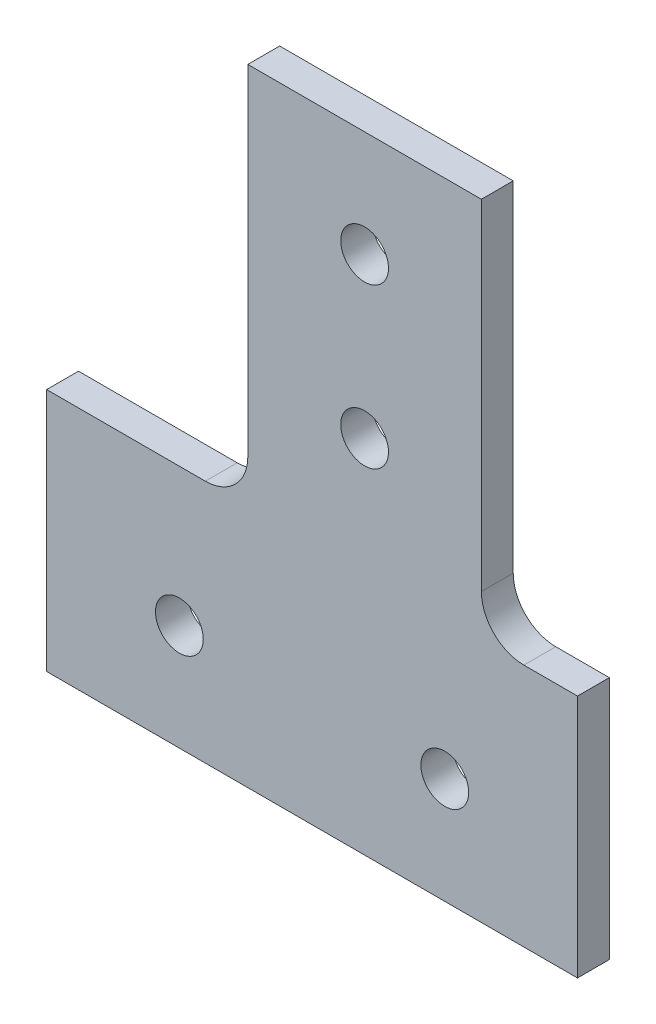
SolidWorks part; units mm, degrees
ref_plane "Ebene vorne" through (0, 0, 0) normal (0, 0, 1) x (1, 0, 0)
ref_plane "Ebene oben" through (0, 0, 0) normal (0, 1, 0) x (1, 0, 0)
ref_plane "Ebene rechts" through (0, 0, 0) normal (1, 0, 0) x (0, 0, -1)
sketch "Skizze1" plane through (0, 0, 0) normal (0, 0, 1) x (1, 0, 0)
  line L0 (-10.0526, 11.5) -> (-25, 11.5)
  line L1 (25, -11.5) -> (-25, -11.5)
  line L2 (25, -11.5) -> (25, 11.5)
  line L3 (25, 11.5) -> (19.9474, 11.5)
  line L4 (-25, -11.5) -> (-25, 11.5)
  line L5 (25, -11.5) -> (-25, 11.5) construction
  line L6 (25, 11.5) -> (-25, -11.5) construction
  line L8 (15.9474, 15.5) -> (15.9474, 71.5)
  line L9 (15.9474, 71.5) -> (-6.0526, 71.5)
  line L10 (-6.0526, 15.5) -> (-6.0526, 71.5)
  arc A0 (19.9474, 11.5) -> (15.9474, 15.5) centre (19.9474, 15.5) cw
  arc A1 (-10.0526, 11.5) -> (-6.0526, 15.5) centre (-10.0526, 15.5) ccw
  point P0 (0, 0)
  point P12 (15.9474, 11.5)
  point P15 (-6.0526, 11.5)
  dimension "D5" = 4
  dimension "D1" = 23
  dimension "D2" = 50
  dimension "D3" = 60
  dimension "D4" = 22
  dimension "D6" = 9.0526
extrude "Aufsatz-Linear austragen1" add sketch "Skizze1" along normal blind 3
hole_wizard "Durchgangsloch für M41" positions "Skizze2" profile "Skizze3" hole size "M4" standard "ANSI Metric" end condition through all
sketch "Skizze2" plane through (0, 0, 3) normal (0, 0, 1) x (1, 0, 0)
  line L1 (4.9474, 53.4879) -> (4.9474, -32.4603) construction
  line L4 (15.9474, 71.5) -> (-6.0526, 71.5) construction
  point P11 (4.9474, 37.5)
  point P13 (4.9474, 22.5)
  dimension "D1" = 15
  dimension "D2" = 34
sketch "Skizze3" plane through (4.9474, 22.5, 3) normal (1, 0, 0) x (0, -1, 0)
  line L0 (0, 0) -> (0, 3)
  line L1 (0, 3) -> (2.25, 3)
  line L2 (2.25, 3) -> (2.25, 0)
  line L5 (2.25, 0) -> (0, 0)
  line L11 (0, -6.35) -> (0, 107.95) construction
  dimension "Bohrerdurchmesser" = 4.5
  dimension "Bohrungstiefe" = 3
hole_wizard "Durchgangsloch für M42" positions "Skizze4" profile "Skizze5" hole size "M4" standard "ANSI Metric" end condition through all
sketch "Skizze4" plane through (0, 0, 3) normal (0, 0, 1) x (1, 0, 0)
  line L3 (0, -11.5) -> (0, -14.3794) construction
  line L7 (-12.5, -1.5) -> (49987.5, -1.5) construction
  line L8 (-25, -11.5) -> (25, -11.5) construction
  point P10 (-12.5, -1.5)
  point P12 (12.5, -1.5)
  dimension "D1" = 25
  dimension "D2" = 12.5
  dimension "D3" = 10
sketch "Skizze5" plane through (-12.5, -1.5, 3) normal (1, 0, 0) x (0, -1, 0)
  line L0 (0, 0) -> (0, 3)
  line L1 (0, 3) -> (2.25, 3)
  line L2 (2.25, 3) -> (2.25, 0)
  line L5 (2.25, 0) -> (0, 0)
  line L11 (0, -6.35) -> (0, 107.95) construction
  dimension "Bohrerdurchmesser" = 4.5
  dimension "Bohrungstiefe" = 3
sketch "Skizze6" plane through (0, 0, 3) normal (0, 0, 1) x (1, 0, 0)
  line L0 (-6.0526, 71.5) -> (15.9474, 71.5)
  line L1 (15.9474, 71.5) -> (15.9474, 47.5)
  line L2 (15.9474, 15.5) -> (15.9474, 71.5) construction
  line L3 (15.9474, 47.5) -> (-6.0526, 47.5)
  line L4 (-6.0526, 71.5) -> (-6.0526, 15.5) construction
  line L5 (-6.0526, 47.5) -> (-6.0526, 71.5)
  dimension "D1" = 24
extrude "Schnitt-Linear austragen1" cut sketch "Skizze6" against normal through all
